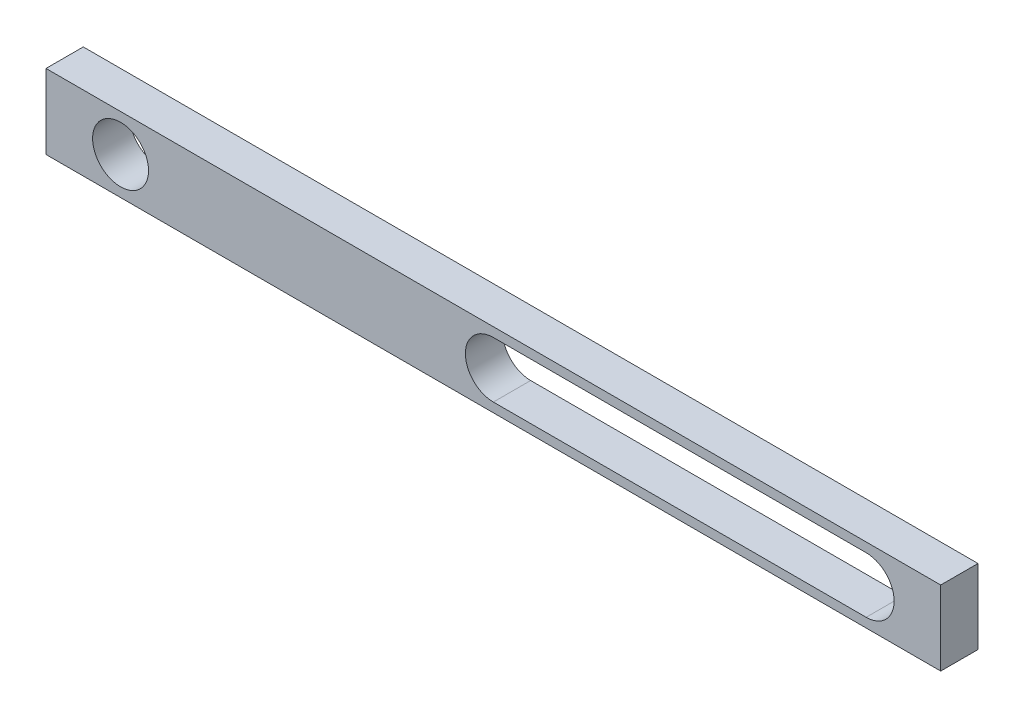
SolidWorks part; units mm, degrees
ref_plane "Front Plane" through (0, 0, 0) normal (0, 0, 1) x (1, 0, 0)
ref_plane "Top Plane" through (0, 0, 0) normal (0, 1, 0) x (1, 0, 0)
ref_plane "Right Plane" through (0, 0, 0) normal (1, 0, 0) x (0, 0, -1)
sketch "Sketch2" plane through (0, 0, 0) normal (0, 0, 1) x (1, 0, 0)
  line L1 (-76.2, -6.35) -> (76.2, -6.35)
  line L2 (-76.2, -6.35) -> (-76.2, 6.35)
  line L3 (-76.2, 6.35) -> (76.2, 6.35)
  line L4 (76.2, -6.35) -> (76.2, 6.35)
  line L5 (-76.2, -6.35) -> (76.2, 6.35) construction
  line L6 (-76.2, 6.35) -> (76.2, -6.35) construction
  line L7 (0, -4.7625) -> (63.5, -4.7625)
  line L9 (0, 4.7625) -> (63.5, 4.7625)
  arc A0 (63.5, -4.7625) -> (63.5, 4.7625) centre (63.5, 0) ccw
  arc A2 (0, 4.7625) -> (0, -4.7625) centre (0, 0) ccw
  circle A3 centre (-63.5, 0) radius 4.7625
  point P0 (0, 0)
  dimension "D3" = 9.525
  dimension "D6" = 9.525
  dimension "D1" = 152.4
  dimension "D2" = 12.7
  dimension "D4" = 6.35
  dimension "D5" = 63.5
  dimension "D7" = 63.5
  dimension "D8" = 6.35
extrude "Boss-Extrude1" add sketch "Sketch2" along normal blind 6.35
